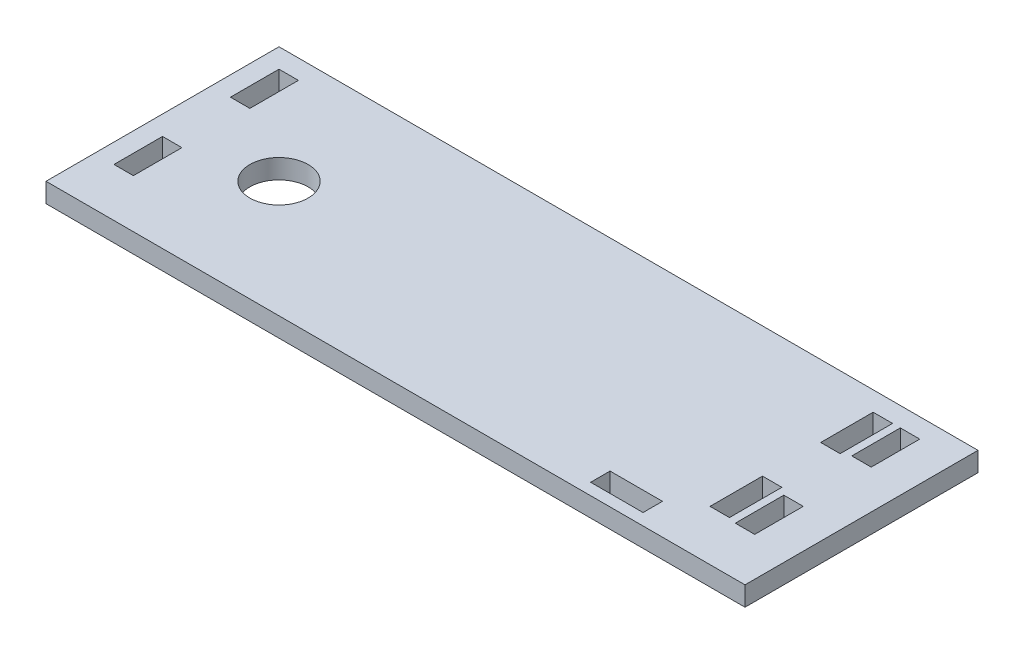
SolidWorks part; units mm, degrees
ref_plane "Front Plane" through (0, 0, 0) normal (0, 0, 1) x (1, 0, 0)
ref_plane "Top Plane" through (0, 0, 0) normal (0, 1, 0) x (1, 0, 0)
ref_plane "Right Plane" through (0, 0, 0) normal (1, 0, 0) x (0, 0, -1)
sketch "Sketch1" plane through (0, 0, 0) normal (0, 1, 0) x (1, 0, 0)
  line L0 (-107.95, -6.35) -> (-101.6, -6.35)
  line L1 (-114.3, 38.1) -> (114.3, 38.1)
  line L2 (-114.3, 38.1) -> (-114.3, -38.1)
  line L3 (-114.3, -38.1) -> (114.3, -38.1)
  line L4 (114.3, 38.1) -> (114.3, -38.1)
  line L5 (-107.95, 31.75) -> (-101.6, 31.75)
  line L6 (-107.95, 31.75) -> (-107.95, 15.875)
  line L7 (-107.95, 15.875) -> (-101.6, 15.875)
  line L8 (-101.6, 31.75) -> (-101.6, 15.875)
  line L9 (-107.95, -6.35) -> (-107.95, -22.225)
  line L10 (-107.95, -22.225) -> (-101.6, -22.225)
  line L11 (-101.6, -6.35) -> (-101.6, -22.225)
  line L12 (86.36, -4.445) -> (86.36, -21.59)
  line L13 (95.25, 31.75) -> (101.6, 31.75)
  line L14 (95.25, 31.75) -> (95.25, 15.875)
  line L15 (95.25, 15.875) -> (101.6, 15.875)
  line L16 (101.6, 31.75) -> (101.6, 15.875)
  line L17 (95.25, -6.35) -> (101.6, -6.35)
  line L18 (95.25, -6.35) -> (95.25, -22.225)
  line L19 (95.25, -22.225) -> (101.6, -22.225)
  line L20 (101.6, -6.35) -> (101.6, -22.225)
  line L21 (86.36, 31.75) -> (92.71, 31.75)
  line L22 (86.36, 31.75) -> (86.36, 14.605)
  line L23 (86.36, 14.605) -> (92.71, 14.605)
  line L24 (92.71, 31.75) -> (92.71, 14.605)
  line L25 (86.36, -4.445) -> (92.71, -4.445)
  line L26 (92.71, -4.445) -> (92.71, -21.59)
  line L27 (86.36, -21.59) -> (92.71, -21.59)
  line L28 (86.36, 31.75) -> (86.36, -4.445) construction
  line L30 (60.0075, -27.94) -> (77.1525, -27.94)
  line L31 (60.0075, -27.94) -> (60.0075, -34.29)
  line L32 (60.0075, -34.29) -> (77.1525, -34.29)
  line L33 (77.1525, -27.94) -> (77.1525, -34.29)
  circle A0 centre (-76.2, 0) radius 9.525
  point P7 (-114.3, 0)
  point P13 (0, 38.1)
  point P39 (77.1525, -31.115)
  dimension "D1" = 19.05
  dimension "D2" = 6.35
  dimension "D3" = 38.1
  dimension "D4" = 190.5
  dimension "D5" = 6.35
  dimension "D6" = 15.875
  dimension "D7" = 6.35
  dimension "D8" = 38.1
  dimension "D9" = 22.225
  dimension "D10" = 196.85
  dimension "D11" = 6.35
  dimension "D12" = 17.145
  dimension "D13" = 162.56
  dimension "D14" = 6.35
  dimension "D16" = 36.195
  dimension "D17" = 6.35
  dimension "D18" = 17.145
  dimension "D19" = 9.2075
  dimension "D20" = 6.35
  dimension "D15" = 2
extrude "Boss-Extrude1" add sketch "Sketch1" along normal blind 6.35
